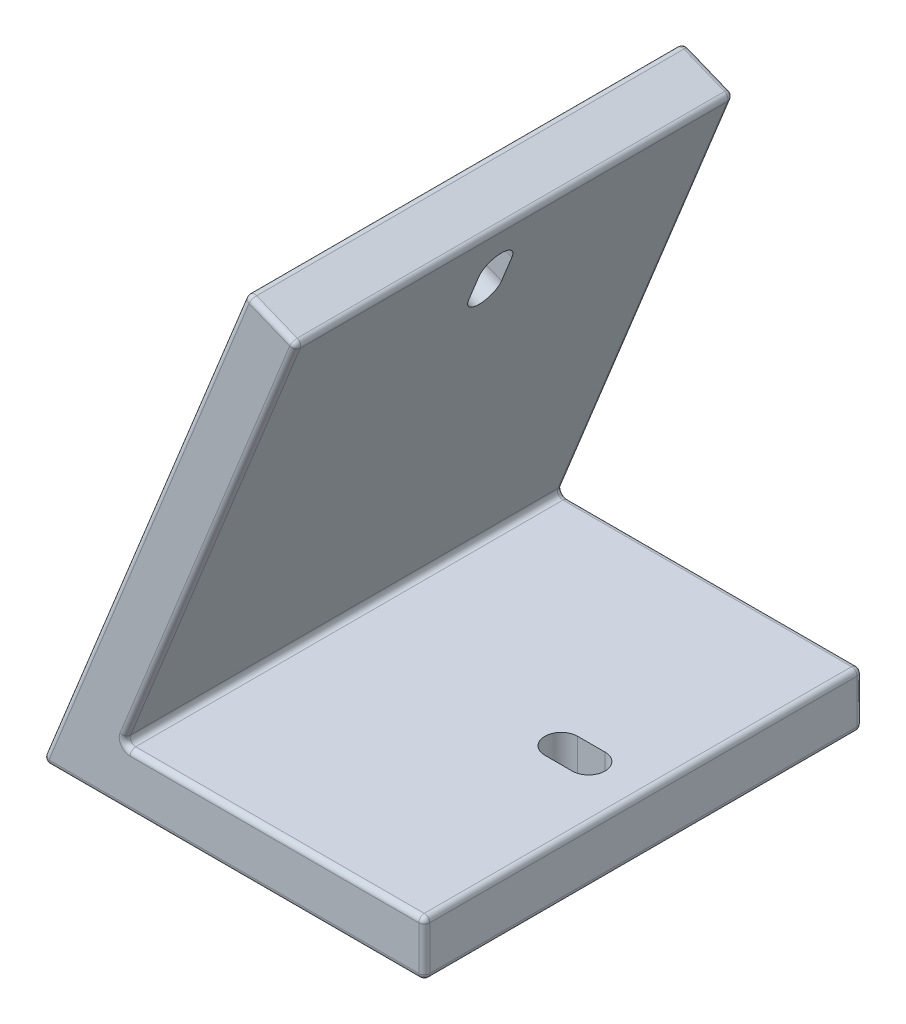
SolidWorks part; units mm, degrees
ref_plane "Front Plane" through (0, 0, 0) normal (0, 0, 1) x (1, 0, 0)
ref_plane "Top Plane" through (0, 0, 0) normal (0, 1, 0) x (1, 0, 0)
ref_plane "Right Plane" through (0, 0, 0) normal (1, 0, 0) x (0, 0, -1)
sketch "Sketch1" plane through (0, 0, 0) normal (0, 0, 1) x (1, 0, 0)
  line L0 (0, 0) -> (37.4607, 92.7184)
  line L1 (0, 0) -> (70, 0)
  line L2 (70, 0) -> (70, 10)
  line L3 (70, 10) -> (14.8256, 10)
  line L4 (14.8256, 10) -> (46.7325, 88.9723)
  line L5 (46.7325, 88.9723) -> (37.4607, 92.7184)
  dimension "D1" = 10
  dimension "D2" = 68
  dimension "D3" = 70
  dimension "D4" = 100
extrude "Boss-Extrude1" add sketch "Sketch1" along normal mid plane 80
sketch "Sketch2" plane through (0, 10, 0) normal (0, 1, 0) x (1, 0, 0)
  line L0 (60, 0) -> (55, 0) construction
  line L1 (60, -3) -> (55, -3)
  line L2 (60, 3) -> (55, 3)
  line L3 (70, -40) -> (70, 40) construction
  arc A0 (60, -3) -> (60, 3) centre (60, 0) ccw
  arc A1 (55, 3) -> (55, -3) centre (55, 0) ccw
  point P3 (57.5, 0)
  dimension "D3" = 3
  dimension "D1" = 5
  dimension "D2" = 10
extrude "Cut-Extrude1" cut sketch "Sketch2" against normal through all
sketch "Sketch3" plane through (9.2718, -3.7461, 0) normal (0.9272, -0.3746, 0) x (0, 0, -1)
  line L0 (0, 90) -> (0, 85) construction
  line L1 (3, 90) -> (3, 85)
  line L2 (-3, 90) -> (-3, 85)
  line L3 (-40, 100) -> (40, 100) construction
  arc A0 (3, 90) -> (-3, 90) centre (0, 90) ccw
  arc A1 (-3, 85) -> (3, 85) centre (0, 85) ccw
  point P3 (0, 87.5)
  dimension "D2" = 3
  dimension "D1" = 5
  dimension "D3" = 10
extrude "Cut-Extrude2" cut sketch "Sketch3" against normal through all
fillet "Fillet1" radius 1 18 edges at (70, 0, 0) (70, 10, 0) (46.7325, 88.9723, 0) (37.4607, 92.7184, 0) (18.7303, 46.3592, 40) (42.0966, 90.8454, 40) (30.7791, 49.4862, 40) (42.4128, 10, 40) (70, 5, 40) (35, 0, 40) (70, 5, -40) (42.4128, 10, -40) (30.7791, 49.4862, -40) (42.0966, 90.8454, -40) (18.7303, 46.3592, -40) (35, 0, -40) (14.8256, 10, 0) (0, 0, 0)
